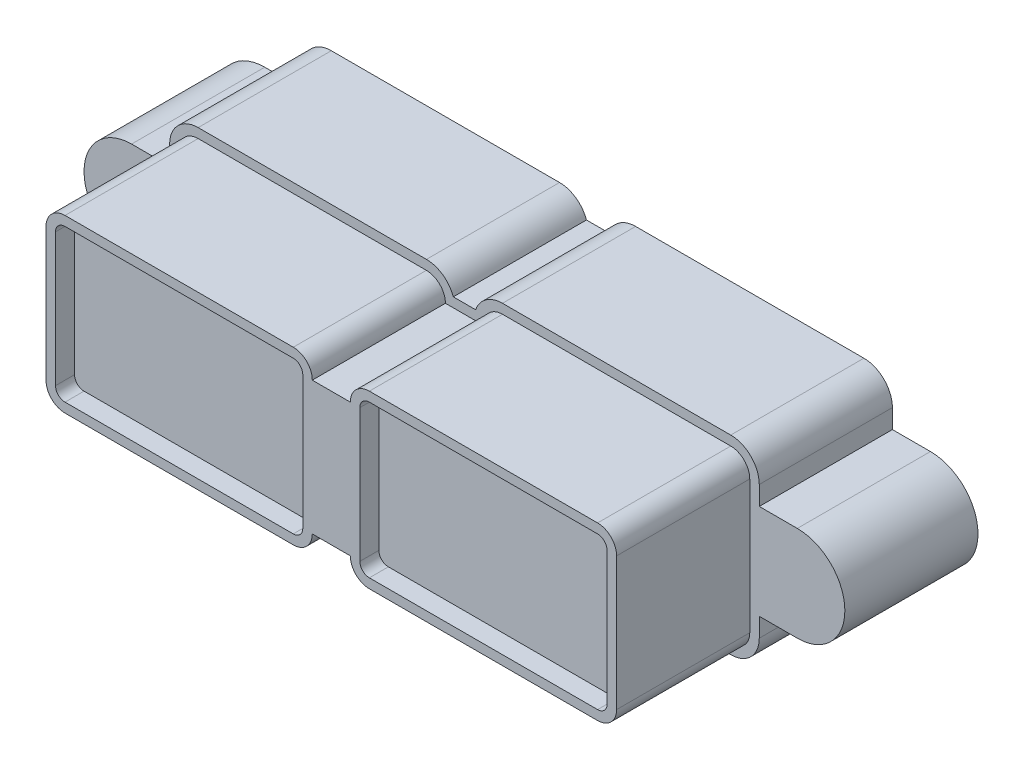
SolidWorks part; units mm, degrees
ref_plane "Front Plane" through (0, 0, 0) normal (0, 0, 1) x (1, 0, 0)
ref_plane "Top Plane" through (0, 0, 0) normal (0, 1, 0) x (1, 0, 0)
ref_plane "Right Plane" through (0, 0, 0) normal (1, 0, 0) x (0, 0, -1)
sketch "Sketch1" plane through (0, 0, 0) normal (0, 0, 1) x (1, 0, 0)
  line L1 (-22.5, 18.75) -> (22.5, 18.75)
  line L2 (-22.5, 18.75) -> (-22.5, -18.75)
  line L3 (-22.5, -18.75) -> (22.5, -18.75)
  line L4 (22.5, 18.75) -> (22.5, -18.75)
  line L5 (-22.5, 18.75) -> (22.5, -18.75) construction
  line L6 (-22.5, -18.75) -> (22.5, 18.75) construction
  point P0 (0, 0)
  dimension "D1" = 37.5
  dimension "D2" = 45
extrude "Boss-Extrude1" add sketch "Sketch1" along normal blind 2
sketch "Sketch2" plane through (0, 0, 2) normal (0, 0, 1) x (1, 0, 0)
  line L0 (0, 18.75) -> (0, -18.75) construction
  line L1 (22.5, 18.75) -> (-22.5, 18.75) construction
  line L2 (-22.5, -18.75) -> (22.5, -18.75) construction
  line L4 (-20, -4.75) -> (20, -4.75)
  line L5 (-20, -4.75) -> (-20, -17.75)
  line L6 (-20, -17.75) -> (20, -17.75)
  line L7 (20, -4.75) -> (20, -17.75)
  line L8 (-20, -4.75) -> (20, -17.75) construction
  line L9 (-20, -17.75) -> (20, -4.75) construction
  point P6 (0, -11.25)
  dimension "D1" = 13
  dimension "D2" = 40
  dimension "D3" = 1
extrude "Boss-Extrude2" add sketch "Sketch2" along normal blind 7
sketch "Sketch3" plane through (0, 0, 9) normal (0, 0, 1) x (1, 0, 0)
  line L0 (0, -4.75) -> (0, -17.75) construction
  line L1 (20, -4.75) -> (-20, -4.75) construction
  line L2 (-20, -17.75) -> (20, -17.75) construction
  line L3 (-1, -7.75) -> (-1, -6.75)
  line L4 (1, -6.75) -> (15, -6.75)
  line L5 (1, -7.75) -> (1, -6.75)
  line L6 (1, -15.75) -> (15, -15.75)
  line L7 (15, -6.75) -> (15, -15.75)
  line L8 (-1, -6.75) -> (-15, -6.75)
  line L9 (1, -14.75) -> (1, -15.75)
  line L10 (-1, -15.75) -> (-15, -15.75)
  line L11 (-15, -6.75) -> (-15, -15.75)
  line L12 (1, -7.75) -> (-1, -7.75)
  line L13 (-1, -14.75) -> (-1, -15.75)
  line L14 (1, -14.75) -> (-1, -14.75)
  line L15 (-20, -17.75) -> (20, -17.75) construction
  point P20 (0, -7.75)
  point P24 (0, -14.75)
  dimension "D1" = 2
  dimension "D2" = 2
  dimension "D3" = 30
  dimension "D5" = 2
  dimension "D6" = 1
  dimension "D7" = 1
extrude "Boss-Extrude3" add sketch "Sketch3" along normal blind 7
fillet "Fillet1" radius 1 8 edges at (-15, -15.75, 12.5) (-1, -15.75, 12.5) (1, -15.75, 12.5) (-15, -6.75, 12.5) (15, -15.75, 12.5) (15, -6.75, 12.5) (1, -6.75, 12.5) (-1, -6.75, 12.5)
sketch "Sketch4" plane through (0, 0, 16) normal (0, 0, 1) x (1, 0, 0)
  line L0 (-1.5, -14.75) -> (-1.5, -7.75)
  line L1 (1.5, -7.75) -> (1.5, -14.75)
  line L48 (-14.5, -7.75) -> (-14.5, -14.75)
  line L49 (-14, -15.25) -> (-2, -15.25)
  line L51 (-2, -14.25) -> (2, -14.25)
  line L53 (2, -15.25) -> (14, -15.25)
  line L54 (14.5, -14.75) -> (14.5, -7.75)
  line L55 (14, -7.25) -> (2, -7.25)
  line L57 (2, -8.25) -> (-2, -8.25)
  line L59 (-2, -7.25) -> (-14, -7.25)
  line L60 (-14.5, -7.75) -> (-14.5, -14.75)
  line L61 (-14, -15.25) -> (-2, -15.25)
  line L65 (2, -15.25) -> (14, -15.25)
  line L66 (14.5, -14.75) -> (14.5, -7.75)
  line L67 (14, -7.25) -> (2, -7.25)
  line L71 (-2, -7.25) -> (-14, -7.25)
  arc A32 (-14.5, -14.75) -> (-14, -15.25) centre (-14, -14.75) ccw
  arc A33 (-2, -15.25) -> (-2, -14.25) centre (-2, -14.75) ccw
  arc A34 (2, -14.25) -> (2, -15.25) centre (2, -14.75) ccw
  arc A35 (14, -15.25) -> (14.5, -14.75) centre (14, -14.75) ccw
  arc A36 (14.5, -7.75) -> (14, -7.25) centre (14, -7.75) ccw
  arc A37 (2, -7.25) -> (2, -8.25) centre (2, -7.75) ccw
  arc A38 (-2, -8.25) -> (-2, -7.25) centre (-2, -7.75) ccw
  arc A39 (-14, -7.25) -> (-14.5, -7.75) centre (-14, -7.75) ccw
  arc A40 (-14.5, -14.75) -> (-14, -15.25) centre (-14, -14.75) ccw
  arc A41 (-2, -15.25) -> (-1.5, -14.75) centre (-2, -14.75) ccw
  arc A42 (1.5, -14.75) -> (2, -15.25) centre (2, -14.75) ccw
  arc A43 (14, -15.25) -> (14.5, -14.75) centre (14, -14.75) ccw
  arc A44 (14.5, -7.75) -> (14, -7.25) centre (14, -7.75) ccw
  arc A45 (2, -7.25) -> (1.5, -7.75) centre (2, -7.75) ccw
  arc A46 (-1.5, -7.75) -> (-2, -7.25) centre (-2, -7.75) ccw
  arc A47 (-14, -7.25) -> (-14.5, -7.75) centre (-14, -7.75) ccw
  dimension "D1" = 0.5
extrude "Cut-Extrude1" cut sketch "Sketch4" against normal blind 1
sketch "Sketch5" plane through (0, 0, 9) normal (0, 0, 1) x (1, 0, 0)
  line L11 (-20, -4.75) -> (-20, -17.75) construction
  line L12 (20, -17.75) -> (20, -4.75) construction
  line L15 (-15.5, -7.75) -> (-15.5, -14.75)
  line L26 (-15.5, -7.75) -> (-15.5, -14.75) construction
  line L27 (-17.5, -8.75) -> (-15.5, -8.75)
  line L28 (15.5, -14.75) -> (15.5, -7.75)
  line L29 (15.5, -14.75) -> (15.5, -7.75) construction
  line L30 (-15.5, -8.75) -> (-15.5, -7.75)
  line L31 (-17.5, -13.75) -> (-15.5, -13.75)
  line L32 (-15.5, -13.75) -> (-15.5, -14.75)
  line L33 (17.5, -13.75) -> (15.5, -13.75)
  line L34 (15.5, -13.75) -> (15.5, -14.75)
  line L35 (17.5, -8.75) -> (15.5, -8.75)
  line L36 (15.5, -8.75) -> (15.5, -7.75)
  line L41 (14, -6.25) -> (2, -6.25)
  line L42 (-2, -6.25) -> (-14, -6.25)
  line L43 (0.5858, -7.25) -> (-0.5858, -7.25)
  line L44 (14, -6.25) -> (2, -6.25)
  line L45 (-2, -6.25) -> (-14, -6.25)
  line L46 (0.5858, -7.25) -> (-0.5858, -7.25)
  line L51 (20.5, -18.25) -> (20.5, -4.25)
  line L52 (-20.5, -18.25) -> (20.5, -18.25)
  line L53 (-20.5, -4.25) -> (-20.5, -18.25)
  line L54 (20.5, -4.25) -> (-20.5, -4.25)
  line L55 (20.5, -18.25) -> (20.5, -4.25)
  line L56 (-20.5, -18.25) -> (20.5, -18.25)
  line L57 (-20.5, -4.25) -> (-20.5, -18.25)
  line L58 (20.5, -4.25) -> (-20.5, -4.25)
  line L65 (2, -16.25) -> (14, -16.25)
  line L66 (-14, -16.25) -> (-2, -16.25)
  line L67 (-0.5858, -15.25) -> (0.5858, -15.25)
  line L68 (2, -16.25) -> (14, -16.25)
  line L69 (-14, -16.25) -> (-2, -16.25)
  line L70 (-0.5858, -15.25) -> (0.5858, -15.25)
  circle A4 centre (-17.5, -11.25) radius 2.5 construction
  circle A5 centre (17.5, -11.25) radius 2.5 construction
  arc A14 (-15.5, -14.75) -> (-14, -16.25) centre (-14, -14.75) ccw
  arc A15 (-14, -6.25) -> (-15.5, -7.75) centre (-14, -7.75) ccw
  arc A16 (-15.5, -14.75) -> (-14, -16.25) centre (-14, -14.75) ccw
  arc A17 (-14, -6.25) -> (-15.5, -7.75) centre (-14, -7.75) ccw
  arc A18 (-17.5, -13.75) -> (-17.5, -8.75) centre (-17.5, -11.25) cw
  arc A19 (17.5, -8.75) -> (17.5, -13.75) centre (17.5, -11.25) cw
  arc A20 (14, -16.25) -> (15.5, -14.75) centre (14, -14.75) ccw
  arc A21 (15.5, -7.75) -> (14, -6.25) centre (14, -7.75) ccw
  arc A22 (14, -16.25) -> (15.5, -14.75) centre (14, -14.75) ccw
  arc A23 (15.5, -7.75) -> (14, -6.25) centre (14, -7.75) ccw
  arc A32 (2, -6.25) -> (0.5858, -7.25) centre (2, -7.75) ccw
  arc A33 (-0.5858, -7.25) -> (-2, -6.25) centre (-2, -7.75) ccw
  arc A34 (2, -6.25) -> (0.5858, -7.25) centre (2, -7.75) ccw
  arc A35 (-0.5858, -7.25) -> (-2, -6.25) centre (-2, -7.75) ccw
  arc A41 (0.5858, -15.25) -> (2, -16.25) centre (2, -14.75) ccw
  arc A42 (-2, -16.25) -> (-0.5858, -15.25) centre (-2, -14.75) ccw
  arc A43 (0.5858, -15.25) -> (2, -16.25) centre (2, -14.75) ccw
  arc A44 (-2, -16.25) -> (-0.5858, -15.25) centre (-2, -14.75) ccw
  point P13 (-20, -11.25)
  dimension "D3" = 5
  dimension "D4" = 0.5
  dimension "D5" = 0.5
  dimension "D6" = 0.5
  dimension "D7" = 0.5
  dimension "D8" = 0.5
extrude "Cut-Extrude2" cut sketch "Sketch5" against normal up to surface (7 mm away) up to face at (0, 0, 2)
sketch "Sketch6" plane through (0, 0, 0) normal (0, 0, -1) x (-1, 0, 0)
  line L0 (0, 18.75) -> (0, -18.75) construction
  line L1 (-22.5, 18.75) -> (22.5, 18.75) construction
  line L2 (22.5, -18.75) -> (-22.5, -18.75) construction
  line L3 (-0.5, 18.25) -> (-0.5, -1.75)
  line L4 (-11.5, 18.25) -> (11.5, 18.25) construction
  line L5 (-11.5, 18.25) -> (-11.5, -1.75)
  line L6 (-11.5, -1.75) -> (11.5, -1.75) construction
  line L7 (11.5, 18.25) -> (11.5, -1.75)
  line L8 (-11.5, 18.25) -> (11.5, -1.75) construction
  line L9 (-11.5, -1.75) -> (11.5, 18.25) construction
  line L10 (-0.5, -1.75) -> (-11.5, -1.75)
  line L11 (-11.5, 18.25) -> (-0.5, 18.25)
  line L12 (11.5, 18.25) -> (0.5, 18.25)
  line L13 (0.5, 18.25) -> (0.5, -1.75)
  line L14 (0.5, -1.75) -> (11.5, -1.75)
  point P6 (0, 8.25)
  dimension "D1" = 20
  dimension "D2" = 23
  dimension "D3" = 11
  dimension "D4" = 0.5
extrude "Boss-Extrude5" add sketch "Sketch6" along normal blind 12
sketch "Sketch7" plane through (0, 18.25, 0) normal (0, 1, 0) x (1, 0, 0)
  line L0 (-11.5, 12) -> (-0.5, 12) construction
  line L1 (-10.5, 10) -> (-1.5, 10)
  line L2 (-10.5, 10) -> (-10.5, 1)
  line L3 (-10.5, 1) -> (-1.5, 1)
  line L4 (-1.5, 10) -> (-1.5, 1)
  line L5 (1.5, 10) -> (10.5, 10)
  line L6 (1.5, 10) -> (1.5, 1)
  line L7 (1.5, 1) -> (10.5, 1)
  line L8 (10.5, 10) -> (10.5, 1)
  line L9 (-11.5, 12) -> (-11.5, 0) construction
  line L10 (-0.5, 12) -> (-0.5, 0) construction
  line L11 (0.5, 12) -> (0.5, 0) construction
  line L12 (0.5, 0) -> (11.5, 0) construction
  dimension "D1" = 2
  dimension "D2" = 1
  dimension "D3" = 1
  dimension "D4" = 1
  dimension "D5" = 1
extrude "Cut-Extrude3" cut sketch "Sketch7" against normal blind 12
sketch "Sketch8" plane through (0, 0, 2) normal (0, 0, 1) x (1, 0, 0)
  line L1 (66.4152, 48.3377) -> (-66.4152, 48.3377)
  line L2 (66.4152, 48.3377) -> (66.4152, -48.3377)
  line L3 (66.4152, -48.3377) -> (-66.4152, -48.3377)
  line L4 (-66.4152, 48.3377) -> (-66.4152, -48.3377)
  line L5 (66.4152, 48.3377) -> (-66.4152, -48.3377) construction
  line L6 (66.4152, -48.3377) -> (-66.4152, 48.3377) construction
  point P0 (0, 0)
extrude "Cut-Extrude4" cut sketch "Sketch8" against normal blind 20
move or copy body "Body-Move/Copy1" [suppressed] bodies to move or copy 110
